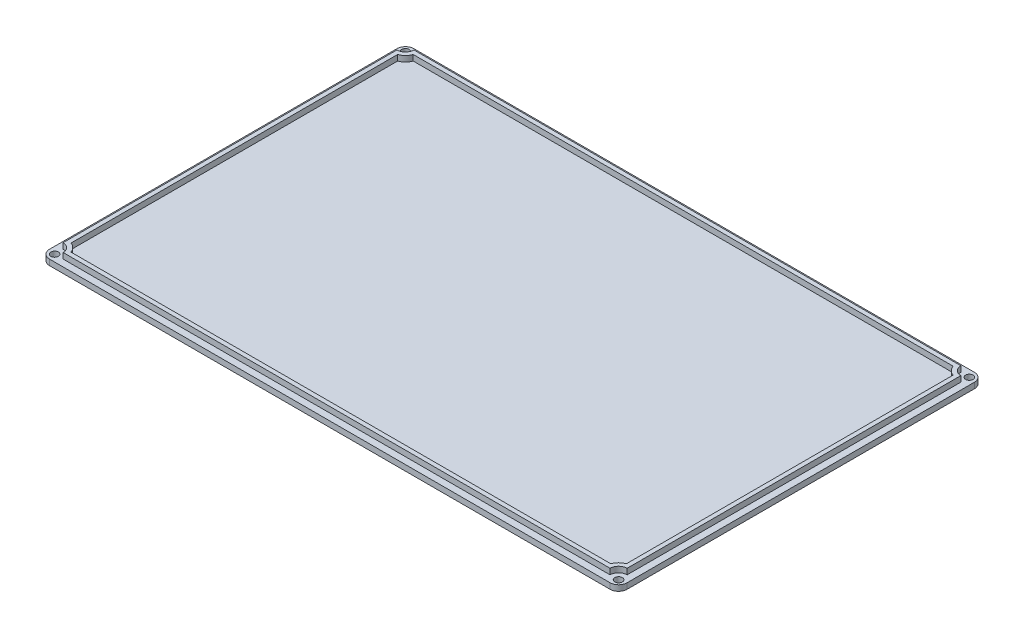
SolidWorks part; units mm, degrees
ref_plane "Front Plane" through (0, 0, 0) normal (0, 0, 1) x (1, 0, 0)
ref_plane "Top Plane" through (0, 0, 0) normal (0, 1, 0) x (1, 0, 0)
ref_plane "Right Plane" through (0, 0, 0) normal (1, 0, 0) x (0, 0, -1)
sketch "Sketch20" plane through (0, 0, 0) normal (0, 1, 0) x (1, 0, 0)
  line L0 (2.572, 21.812) -> (165.484, 21.812)
  line L1 (-2, 128.336) -> (170.056, 128.336)
  line L2 (-2, 128.336) -> (-2, 19.78)
  line L3 (-2, 19.78) -> (170.056, 19.78)
  line L4 (170.056, 128.336) -> (170.056, 19.78)
  line L5 (0.032, 123.764) -> (0.032, 24.352)
  line L10 (2.572, 126.304) -> (165.484, 126.304)
  line L11 (168.024, 123.764) -> (168.024, 24.352)
  line L15 (3.6241, 23.082) -> (164.4319, 23.082)
  line L16 (1.302, 122.7119) -> (1.302, 25.4041)
  line L17 (3.6241, 125.034) -> (164.4319, 125.034)
  line L18 (166.754, 122.7119) -> (166.754, 25.4041)
  arc A0 (0.032, 123.764) -> (2.572, 126.304) centre (0.032, 126.304) ccw
  arc A1 (0.032, 24.352) -> (2.572, 21.812) centre (0.032, 21.812) cw
  arc A2 (165.484, 126.304) -> (168.024, 123.764) centre (168.024, 126.304) ccw
  arc A3 (165.484, 21.812) -> (168.024, 24.352) centre (168.024, 21.812) cw
  arc A5 (1.302, 122.7119) -> (3.6241, 125.034) centre (0.032, 126.304) ccw
  arc A6 (1.302, 25.4041) -> (3.6241, 23.082) centre (0.032, 21.812) cw
  arc A7 (164.4319, 125.034) -> (166.754, 122.7119) centre (168.024, 126.304) ccw
  arc A8 (164.4319, 23.082) -> (166.754, 25.4041) centre (168.024, 21.812) cw
  dimension "D21" = 2.54
  dimension "D22" = 2.54
  dimension "D23" = 2.54
  dimension "D24" = 2.54
  dimension "D30" = 1.27
  dimension "D31" = 3.81
  dimension "D32" = 3.81
  dimension "D33" = 3.81
  dimension "D28" = 3.81
  dimension "D2" = 108.556
  dimension "D4" = 172.056
  dimension "D7" = 2.032
  dimension "D8" = 2.032
  dimension "D9" = 2.032
  dimension "D10" = 2.032
  dimension "D13" = 4.572
  dimension "D14" = 4.572
  dimension "D15" = 4.572
  dimension "D16" = 4.572
  dimension "D17" = 4.572
  dimension "D18" = 4.572
  dimension "D19" = 4.572
  dimension "D20" = 4.572
  dimension "D25" = 1.27
  dimension "D26" = 1.27
  dimension "D27" = 1.27
extrude "Boss-Extrude5" add sketch "Sketch20" against normal blind 1.7 separate body contours L4 L3 L2 L1
extrude "Boss-Extrude6" add sketch "Sketch20<3>" along normal blind 1.7 contours L17 A7 L18 A8 L15 A6 L16 A5 | L10 A2 L11 A3 L0 A1 L5 A0
sketch "Sketch20<3>" plane through (0, 0, 0) normal (0, 1, 0) x (1, 0, 0) same geometry as "Sketch20"
fillet "Fillet3" radius 2.54 4 edges at (-2, -0.85, -19.78) (-2, -0.85, -128.336) (170.056, -0.85, -128.336) (170.056, -0.85, -19.78)
hole_wizard "#4-40 Tapped Hole3" positions "Sketch27" profile "Sketch25" tap size "#4-40" standard "ANSI Inch" end condition through all
sketch "Sketch27" plane through (0, 0, 0) normal (0, 1, 0) x (1, 0, 0)
  point P0 (0.032, 21.812)
  point P3 (168.024, 21.812)
  point P6 (168.024, 126.304)
  point P9 (0.032, 126.304)
sketch "Sketch25" plane through (0.032, 0, -21.812) normal (1, 0, 0) x (0, 0, 1)
  line L0 (0, 0) -> (0, 1.7)
  line L1 (0, 1.7) -> (1.1303, 1.7)
  line L2 (1.1303, 1.7) -> (1.1303, 0)
  line L5 (1.1303, 0) -> (0, 0)
  line L11 (0, -6.35) -> (0, 107.95) construction
  dimension "Thru Tap Drill Dia." = 2.2606
  dimension "Thru Tap Drill Depth" = 1.7
cosmetic thread "Hole Thread15"
cosmetic thread "Hole Thread16"
cosmetic thread "Hole Thread17"
cosmetic thread "Hole Thread18"
